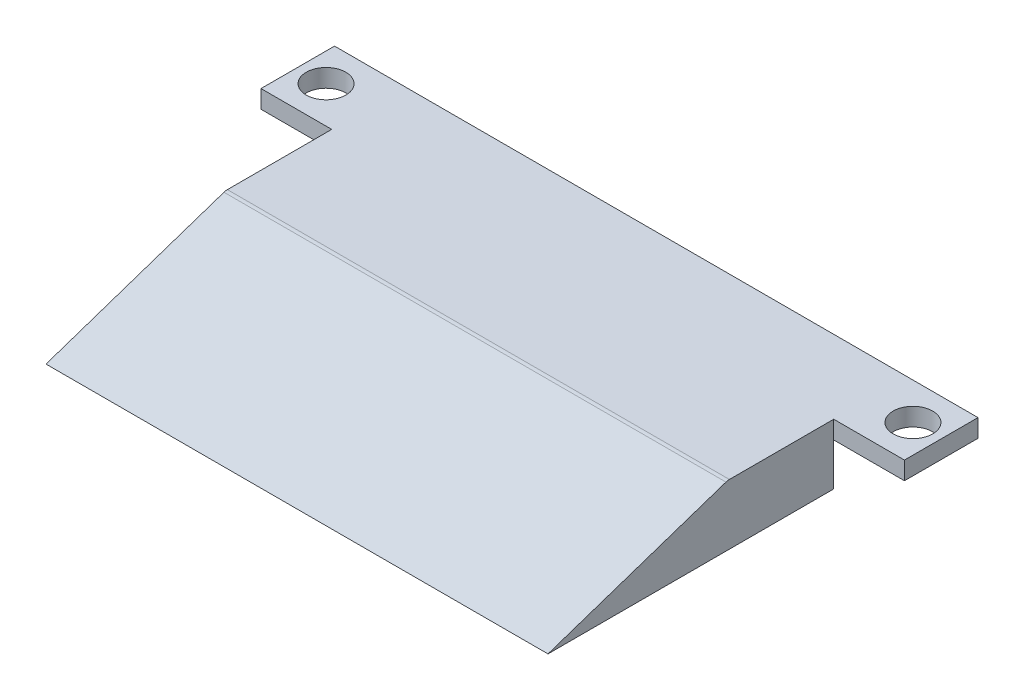
SolidWorks part; units mm, degrees
material "AISI 316 Stainless Steel Sheet (SS)"
ref_plane "Front Plane" through (0, 0, 0) normal (0, 0, 1) x (1, 0, 0)
ref_plane "Top Plane" through (0, 0, 0) normal (0, 1, 0) x (1, 0, 0)
ref_plane "Right Plane" through (0, 0, 0) normal (1, 0, 0) x (0, 0, -1)
sketch "Sketch2" plane through (0, 0, 0) normal (0, 1, 0) x (1, 0, 0)
  line L1 (0, 0) -> (454.914, 0)
  line L2 (0, 0) -> (0, 254)
  line L3 (0, 254) -> (454.914, 254)
  line L4 (454.914, 0) -> (454.914, 254)
  dimension "D1" = 254
  dimension "D2" = 454.914
extrude "Boss-Extrude2" add sketch "Sketch2" along normal blind 42.7
sketch "Sketch5" plane through (0, 42.7, 0) normal (0, 1, 0) x (1, 0, 0)
  line L1 (0, 0) -> (50, 0)
  line L2 (0, 0) -> (0, 202)
  line L3 (0, 202) -> (50, 202)
  line L4 (50, 0) -> (50, 202)
  line L5 (454.914, 0) -> (404.914, 0)
  line L6 (454.914, 0) -> (454.914, 202)
  line L7 (454.914, 202) -> (404.914, 202)
  line L8 (404.914, 0) -> (404.914, 202)
  point P10 (429.914, 0)
  dimension "D1" = 50
  dimension "D2" = 50
  dimension "D3" = 202
  dimension "D4" = 202
extrude "Cut-Extrude2" cut sketch "Sketch5" against normal through all
sketch "Sketch6" plane through (0, 42.7, 0) normal (0, 1, 0) x (1, 0, 0)
  line L0 (454.914, 202) -> (454.914, 254) construction
  line L1 (454.914, 202) -> (404.914, 202) construction
  line L3 (0, 254) -> (0, 202) construction
  line L4 (50, 202) -> (0, 202) construction
  circle A0 centre (434.914, 228) radius 14
  circle A1 centre (20, 228) radius 14
  dimension "D1" = 28
  dimension "D2" = 20
  dimension "D4" = 28
  dimension "D5" = 20
  dimension "D6" = 26
  dimension "D3" = 26
extrude "Cut-Extrude3" cut sketch "Sketch6" against normal through all
sketch "Sketch7" plane through (404.914, 0, 0) normal (1, 0, 0) x (0, 0, -1)
  line L0 (0, 42.7) -> (127, 42.7)
  line L1 (202, 42.7) -> (0, 42.7) construction
  line L2 (127, 42.7) -> (0, 0)
  line L3 (0, 0) -> (0, 42.7)
  dimension "5" = 127
extrude "Cut-Extrude4" cut sketch "Sketch7" against normal through all
fillet "Fillet1" radius 7.62 1 edges at (227.457, 42.7, -127)
sketch "Sketch8" plane through (454.914, 0, 0) normal (1, 0, 0) x (0, 0, -1)
  line L0 (202, 0) -> (202, 42.7) construction
  line L1 (254, 0) -> (202, 0)
  line L2 (254, 0) -> (254, 30)
  line L3 (254, 30) -> (202, 30)
  line L4 (202, 0) -> (202, 30)
  dimension "D1" = 30
extrude "Cut-Extrude5" cut sketch "Sketch8" against normal through all
